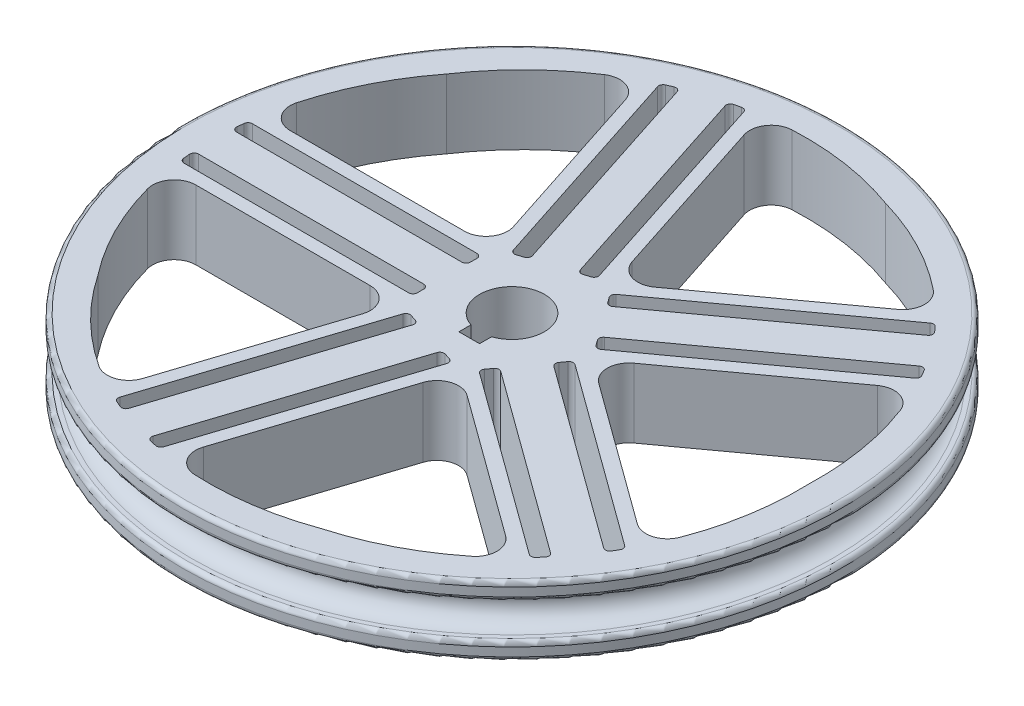
SolidWorks part; units mm, degrees
material "6061 Alloy"
ref_plane "Front Plane" through (0, 0, 0) normal (0, 0, 1) x (1, 0, 0)
ref_plane "Top Plane" through (0, 0, 0) normal (0, 1, 0) x (1, 0, 0)
ref_plane "Right Plane" through (0, 0, 0) normal (1, 0, 0) x (0, 0, -1)
sketch "Sketch1" plane through (0, 0, 0) normal (0, 0, 1) x (1, 0, 0)
  line L3 (0, 8) -> (-1, 8)
  line L4 (0, 0) -> (-1, 0)
  line L5 (-2, 9) -> (-2, 11)
  line L6 (-1, 12) -> (74.2, 12)
  line L7 (0, 4) -> (7.1457, 4) construction
  line L8 (-2, -1) -> (-2, -3)
  line L9 (-1, -4) -> (74.2, -4)
  line L10 (74.2, 12) -> (74.2, -4)
  arc A1 (0, 8) -> (0, 0) centre (0, 4) cw
  arc A2 (-1, 8) -> (-2, 9) centre (-1, 9) cw
  arc A3 (-1, 0) -> (-2, -1) centre (-1, -1) ccw
  arc A4 (-2, 11) -> (-1, 12) centre (-1, 11) cw
  arc A5 (-2, -3) -> (-1, -4) centre (-1, -3) ccw
  point P14 (-2, 8)
  point P17 (-2, 0)
  point P20 (-2, 12)
  point P23 (-2, -4)
  dimension "D2" = 4
  dimension "D7" = 1
  dimension "D8" = 1
  dimension "D1" = 8
  dimension "D3" = 2
  dimension "D4" = 2
  dimension "D5" = 76.2
  dimension "D6" = 4
revolve "Revolve2" add sketch "Sketch1" angle 360 about L10
sketch "Sketch2" plane through (0, -4, 0) normal (0, -1, 0) x (1, 0, 0)
  line L5 (71.2, 0) -> (128.6984, 0) construction
  circle A0 centre (74.2, 0) radius 7.5
  dimension "D1" = 15
extrude "Cut-Extrude3" cut sketch "Sketch2" against normal through all
sketch "Sketch3" plane through (0, -4, 0) normal (0, -1, 0) x (1, 0, 0)
  line L0 (71.2, 0) -> (130.5671, 0) construction
  line L2 (92.741, 0) -> (79.9295, 17.6336)
  line L3 (79.9295, 17.6336) -> (59.2, 10.8981)
  line L4 (59.2, 10.8981) -> (59.2, -10.8981)
  line L5 (59.2, -10.8981) -> (79.9295, -17.6336)
  line L6 (79.9295, -17.6336) -> (92.741, 0)
  line L7 (74.2, 0) -> (79.9295, 17.6336)
  line L8 (79.9295, 17.6336) -> (95.3803, 65.1864)
  line L9 (74.2, 0) -> (92.741, 0)
  line L10 (92.741, 0) -> (142.741, 0)
  line L11 (83.7501, 12.3749) -> (127.5759, 44.2162)
  line L12 (88.9204, 5.2586) -> (132.7462, 37.0999)
  line L13 (79.9295, 17.6336) -> (123.1357, 49.0247)
  line L14 (81.6928, 15.2065) -> (125.2514, 46.8536)
  line L15 (92.741, 0) -> (135.9473, 31.3912)
  line L16 (90.9777, 2.4271) -> (134.5362, 34.0742)
  circle A1 centre (74.2, 0) radius 15 construction
  arc A2 (95.3803, 65.1864) -> (142.741, 0) centre (77.3306, 2.2745) cw
  point P24 (0, 0)
  dimension "D5" = 90
  dimension "D6" = 90
  dimension "D7" = 6.5
  dimension "D1" = 30
  dimension "D4" = 65.45
  dimension "D2" = 50
  dimension "D3" = 50
  dimension "D8" = 6.5
  dimension "D9" = 3
  dimension "D10" = 90
  dimension "D11" = 3
sketch "Sketch5" plane through (0, -4, 0) normal (0, -1, 0) x (1, 0, 0)
  line L0 (74.2, 0) -> (74.2, 9.89)
  line L1 (71.81, 9.89) -> (76.59, 9.89)
  line L4 (74.2, 9.89) -> (74.2, 7.5)
  line L5 (71.81, 9.89) -> (71.81, 6.6936)
  line L6 (76.59, 9.89) -> (76.59, 6.6936)
  line L7 (71.81, 6.6936) -> (76.59, 6.6936)
  circle A1 centre (74.2, 0) radius 7.5 construction
  circle M28 centre (74.2, 0) radius 7.5
  dimension "D2" = 2.39
  dimension "D1" = 2.39
extrude "Cut-Extrude5" cut sketch "Sketch5" against normal through all contours L1 L0 M28 | L6 L1 L0 M28 | L0 M28 | L0 L6 M28 region at (72.9743, -4, 8.6279) region at (75.2807, -4, 7.0423) region at (75.4257, -4, 8.6279) region at (73.1193, -4, 7.0423)
extrude "Cut-Extrude7" cut sketch "Sketch3" against normal through all both and the other way through all contours A2 L8 L13 | A2 L14 L2 L11 | A2 L12 L2 L16 | A2 L15 L10 region at (124.6569, -4, 10.7441) region at (111.8005, -4, 19.7211) region at (100.0103, -4, 44.6672) region at (104.5751, -4, 29.6661)
pattern_circular "CirPattern1" count 5 over 360 about axis through (74.2, -4, 0) along (0, -1, 0) of "Cut-Extrude7"
fillet "Fillet1" radius 5 5 edges at (79.9295, 4, -17.6336) (92.741, 4, 0) (79.9295, 4, 17.6336) (59.2, 4, 10.8981) (59.2, 4, -10.8981)
fillet "Fillet2" radius 5 10 edges at (123.1357, 4, 49.0247) (135.9473, 4, 31.3912) (135.9473, 4, -31.3912) (123.1357, 4, -49.0247) (42.6967, 4, -61.6901) (63.4262, 4, -68.4256) (5.7941, 4, -10.8981) (5.7941, 4, 10.8981) (42.6967, 4, 61.6901) (63.4262, 4, 68.4256)
fillet "Fillet3" radius 1 40 edges at (134.5362, 4, -34.0742) (127.5759, 4, -44.2162) (125.2514, 4, -46.8536) (132.7462, 4, -37.0999) (60.4385, 4, -67.9126) (48.6419, 4, -64.427) (57.0077, 4, -67.1452) (45.4153, 4, -63.0313) (5.0284, 4, 4.3981) (5.3587, 4, -7.8981) (5.0284, 4, -4.3981) (5.3587, 4, 7.8981) (60.4385, 4, 67.9126) (48.6419, 4, 64.427) (45.4153, 4, 63.0313) (57.0077, 4, 67.1452) (62.0532, 4, 11.8252) (73.7476, 4, 15.6249) (77.0763, 4, 16.7065) (65.3819, 4, 12.9067) (59.2, 4, 4.3981) (59.2, 4, -7.8981) (59.2, 4, 7.8981) (59.2, 4, -4.3981) (77.0763, 4, -16.7065) (65.3819, 4, -12.9067) (62.0532, 4, -11.8252) (73.7476, 4, -15.6249) (83.7501, 4, -12.3749) (90.9777, 4, -2.4271) (81.6928, 4, -15.2065) (88.9204, 4, -5.2586) (88.9204, 4, 5.2586) (90.9777, 4, 2.4271) (134.5362, 4, 34.0742) (132.7462, 4, 37.0999) (125.2514, 4, 46.8536) (127.5759, 4, 44.2162) (83.7501, 4, 12.3749) (81.6928, 4, 15.2065)
